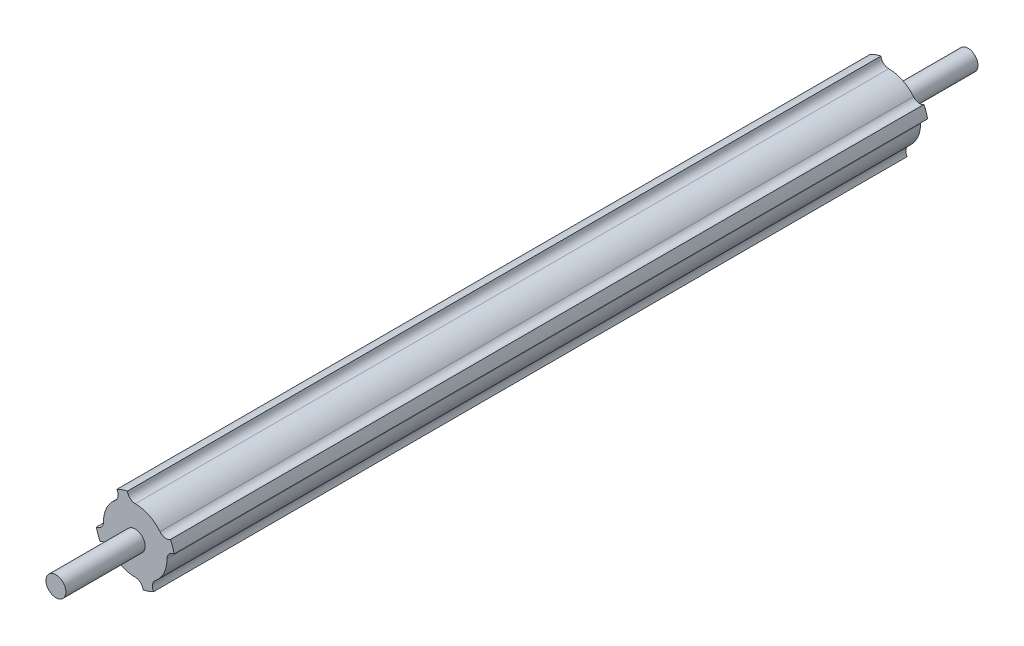
SolidWorks part; units mm, degrees
material "Rubber"
ref_plane "Front Plane" through (0, 0, 0) normal (0, 0, 1) x (1, 0, 0)
ref_plane "Top Plane" through (0, 0, 0) normal (0, 1, 0) x (1, 0, 0)
ref_plane "Right Plane" through (0, 0, 0) normal (1, 0, 0) x (0, 0, -1)
sketch "Sketch1" plane through (0, 0, 0) normal (0, 0, 1) x (1, 0, 0)
  circle A0 centre (0, 0) radius 25.4
extrude "Boss-Extrude1" add sketch "Sketch1" along normal blind 584.2 contours A0
sketch "Sketch2" plane through (0, 0, 0) normal (0, 0, 1) x (1, 0, 0)
  circle A0 centre (0, 0) radius 6.3619
extrude "Cut-Extrude1" cut sketch "Sketch2" along normal blind 50.8 flip side to cut contours A0
sketch "Sketch5" plane through (0, 0, 584.2) normal (0, 0, 1) x (1, 0, 0)
  circle A0 centre (0, 0) radius 6.3779
extrude "Cut-Extrude4" cut sketch "Sketch5" against normal blind 50.8 flip side to cut
ref_axis "Axis1" through (0, 0, 533.4) along (0, 0, -1)
sketch "Sketch13" plane through (0, 0, 584.2) normal (0, 0, 1) x (1, 0, 0)
  arc A0 (0, 25.4) -> (19.7488, 15.9733) centre (0, 0) cw construction
  circle A1 centre (0, 0) radius 25.4 construction
  arc A2 (23.6482, 19.1273) -> (0, 30.4153) centre (0, 0) ccw
  arc A3 (15.8493, 12.8193) -> (0, 20.3847) centre (0, 0) ccw
  arc A4 (15.8493, 12.8193) -> (23.6482, 19.1273) centre (19.7488, 15.9733) ccw
  arc A5 (0, 30.4153) -> (0, 20.3847) centre (0, 25.4) ccw
  point P6 (10.9416, 22.9225)
extrude "Cut-Extrude5" cut sketch "Sketch13" against normal blind 535.94
pattern_circular "CirPattern1" count 4 over 360 about axis through (0, 0, 533.4) along (0, 0, -1) of "Cut-Extrude5"
